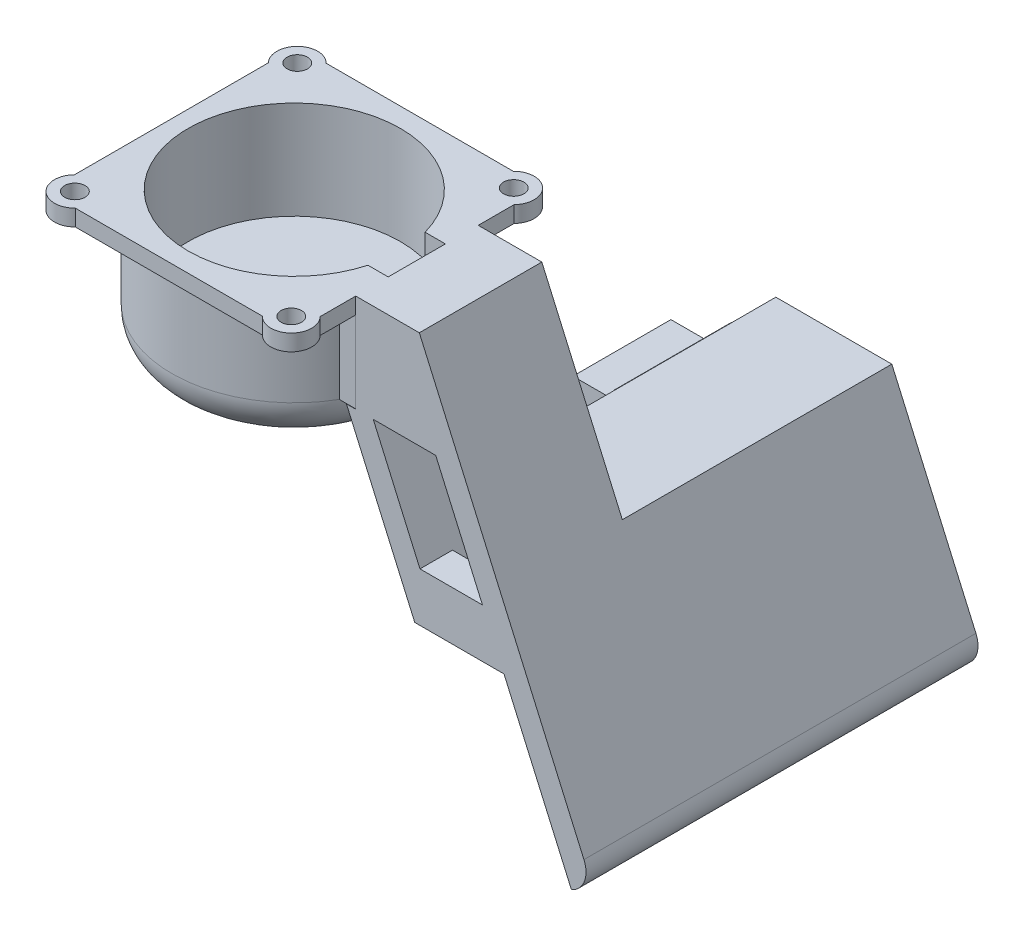
SolidWorks part; units mm, degrees
ref_plane "Front Plane" through (0, 0, 0) normal (0, 0, 1) x (1, 0, 0)
ref_plane "Top Plane" through (0, 0, 0) normal (0, 1, 0) x (1, 0, 0)
ref_plane "Right Plane" through (0, 0, 0) normal (1, 0, 0) x (0, 0, -1)
sketch "Sketch1" plane through (0, 0, 0) normal (0, 1, 0) x (1, 0, 0)
  line L0 (0, 15) -> (13, 15)
  line L1 (13, 15) -> (13, -15)
  line L2 (13, -15) -> (15, -15)
  line L3 (15, -15) -> (15, 15)
  line L4 (15, 15) -> (13, 15)
  circle A0 centre (0, 0) radius 13
  circle A1 centre (0, 0) radius 15
  dimension "D1" = 26
  dimension "D2" = 2
extrude "Boss-Extrude3" add sketch "Sketch1" along normal blind 12 contours L1 A1 A0 | L1 A1 | A1 L1 L2 L3 | A1 L3 L4 L1
sketch "Sketch4" plane through (0, 0, 0) normal (0, -1, 0) x (1, 0, 0)
  circle A0 centre (0, 0) radius 15
extrude "Boss-Extrude4" add sketch "Sketch4" along normal blind 5
fillet "Fillet4" radius 5 1 edges at (0, -5, -15)
sketch "Sketch7" plane through (15, 0, 0) normal (1, 0, 0) x (0, 0, -1)
  line L0 (-15, 0) -> (0, 0) construction
  line L1 (-3.5, 12) -> (3.5, 12)
  line L2 (-3.5, 12) -> (-3.5, 2)
  line L3 (-3.5, 2) -> (3.5, 2)
  line L4 (3.5, 12) -> (3.5, 2)
  line L6 (-15, 12) -> (-15, 0) construction
  dimension "D1" = 10
  dimension "D2" = 2
  dimension "D3" = 7
  dimension "D4" = 11.5
extrude "Cut-Extrude3" cut sketch "Sketch7" against normal blind 18
sketch "Sketch10" plane through (13, 0, 0) normal (-1, 0, 0) x (0, 0, 1)
  line L1 (-15, 12) -> (-7.4833, 12)
  line L2 (-15, 12) -> (-15, 0)
  line L3 (-15, 0) -> (-7.4833, 0)
  line L4 (-7.4833, 12) -> (-7.4833, 0)
  line L5 (7.4833, 12) -> (15, 12)
  line L6 (7.4833, 12) -> (7.4833, 0)
  line L7 (7.4833, 0) -> (15, 0)
  line L8 (15, 12) -> (15, 0)
extrude "Cut-Extrude4" cut sketch "Sketch10" against normal blind 18
sketch "Sketch11" plane through (0, 0, -7.4833) normal (0, 0, -1) x (-1, 0, 0)
  line L0 (-15, 0) -> (-26.4461, -25.9994)
  line L1 (-15, 12) -> (-22.8285, 12)
  line L2 (-22.8285, 12) -> (-40.97, -29.2075)
  line L3 (-26.4461, -25.9994) -> (-7.8394, -25.9994)
  line L4 (-40.97, -29.2075) -> (-44.8405, -37.9994)
  line L5 (-44.8405, -37.9994) -> (-8.2889, -37.9994)
  line L6 (-15, 2) -> (-16.3047, 2)
  line L7 (-15, 0) -> (-15, 12) construction
  line L8 (-16.3047, 2) -> (-29.5119, -27.9994)
  line L9 (-29.5119, -27.9994) -> (-4.9904, -27.9994)
  line L10 (-15, 9) -> (-20.8714, 9)
  line L11 (-20.8714, 9) -> (-40.2419, -34.9994)
  line L12 (-40.2419, -34.9994) -> (-10.0643, -34.9994)
  line L13 (-10.0643, -27.9994) -> (-10.0643, -25.9994)
  line L14 (-10.0643, -25.9994) -> (-10.0643, -27.9994)
  line L15 (-26.4461, -25.9994) -> (-15, 0)
  line L16 (-15, 2) -> (-16.3047, 2)
  line L17 (-15, 0) -> (-15, 2)
  line L18 (-15, 9) -> (-15, 12)
  line L19 (-15, 9) -> (-20.8714, 9)
  line L20 (-15, 12) -> (-22.8285, 12)
  line L21 (-10.0643, -34.9994) -> (-10.0643, -37.9994)
  line L22 (15, 0) -> (-13, 0) construction
  line M15 (-15, 12) -> (-15, 0)
  dimension "D1" = 12
  dimension "D2" = 12
  dimension "D3" = 2
  dimension "D4" = 2
  dimension "D5" = 3
  dimension "2" = 2
  dimension "D6" = 3
  dimension "D7" = 3
  dimension "D8" = 0
extrude "Boss-Extrude7" add sketch "Sketch11" against normal blind 15 contours L21 L12 L11 L10 L1 L2 L4 L5 M15 | L9 L13 L3 L0 L6 L8 M15
fillet "Fillet5" radius 2 2 edges at (26.4461, -25.9994, 0.0167) (29.5119, -27.9994, 0.0167)
fillet "Fillet6" radius 3 2 edges at (40.2419, -34.9994, 0.0167) (44.8405, -37.9994, 0.0167)
sketch "Sketch14" plane through (0, 0, -7.4833) normal (0, 0, -1) x (-1, 0, 0)
  line L0 (-10.0643, -27.9994) -> (-29.5119, -27.9994)
  line L1 (-29.5119, -27.9994) -> (-16.3047, 2)
  line L2 (-16.3047, 2) -> (-15, 2)
  line L3 (-15, 2) -> (-15, 9)
  line L4 (-15, 9) -> (-20.8714, 9)
  line L5 (-20.8714, 9) -> (-40.2419, -34.9994)
  line L6 (-40.2419, -34.9994) -> (-10.0643, -34.9994)
  line L7 (-10.0643, -34.9994) -> (-10.0643, -37.9994)
  line L8 (-10.0643, -37.9994) -> (-44.8405, -37.9994)
  line L9 (-44.8405, -37.9994) -> (-22.8285, 12)
  line L10 (-22.8285, 12) -> (-13, 12)
  line L11 (-13, 12) -> (-13, 0)
  line L12 (-13, 0) -> (-15, 0)
  line L15 (-10.0643, -26.3218) -> (-10.0643, -27.9994)
  line L16 (-22.8285, 12) -> (-42.9876, -33.7906) construction
  line L17 (-16.3047, 2) -> (-28.2766, -25.1935) construction
  line L18 (-15, 9) -> (-20.8714, 9) construction
  line L19 (-40.2419, -37.9994) -> (-10.0643, -37.9994) construction
  line L20 (-15, 2) -> (-15, 9) construction
  line L22 (-20.8714, 9) -> (-38.389, -30.7906) construction
  line L24 (-15, 2) -> (-16.3047, 2) construction
  line L25 (-15, 0) -> (-26.4461, -25.9994)
  line L26 (-26.4461, -25.9994) -> (-10.0643, -25.9994)
  line L27 (-23.3804, -25.9994) -> (-10.0643, -25.9994) construction
  line L28 (-35.6433, -34.9994) -> (-10.0643, -34.9994) construction
  line L29 (-10.0643, -27.9994) -> (-10.0643, -34.9994)
  line M16 (-10.0643, -34.9994) -> (-35.6433, -34.9994)
  arc M17 (-35.6433, -34.9994) -> (-38.389, -30.7906) centre (-35.6433, -31.9994) cw
  line M18 (-38.389, -30.7906) -> (-20.8714, 9)
  line M19 (-20.8714, 9) -> (-15, 9)
  line M20 (-15, 9) -> (-15, 2)
  line M21 (-15, 2) -> (-16.3047, 2)
  line M22 (-16.3047, 2) -> (-28.2766, -25.1935)
  arc M23 (-28.2766, -25.1935) -> (-26.4461, -27.9994) centre (-26.4461, -25.9994) ccw
  line M24 (-26.4461, -27.9994) -> (-10.0643, -27.9994)
  dimension "D1" = 0
  dimension "D2" = 0
  dimension "D3" = 0
  dimension "D4" = 0
  dimension "D5" = 0
  dimension "D6" = 0
  dimension "D7" = 0
extrude "Boss-Extrude10" add sketch "Sketch14" against normal blind 3.98 contours L29 L0 L1 M24 M22 M21 M20 M19 M18 M17 M16 | L1 L0 M23
sketch "Sketch16" plane through (0, 0, 7.5167) normal (0, 0, 1) x (1, 0, 0)
  line L0 (15, 0) -> (26.7788, -25.9994)
  line L1 (26.7788, -25.9994) -> (10.0643, -25.9994)
  line L2 (10.0643, -25.9994) -> (10.0643, -37.9994)
  line L3 (10.0643, -37.9994) -> (44.8405, -37.9994)
  line L4 (44.8405, -37.9994) -> (22.423, 12.921)
  line L6 (15, 12) -> (15, 0)
  line L7 (10.0643, -27.9994) -> (10.0643, -34.9994) construction
  line L8 (23.3804, -25.9994) -> (10.0643, -25.9994) construction
  line L9 (40.2419, -37.9994) -> (10.0643, -37.9994) construction
  line L10 (22.8285, 12) -> (42.9876, -33.7906) construction
  line L12 (15, 12) -> (22.8285, 12)
  line M5 (10.0643, -27.9994) -> (26.4461, -27.9994)
  arc M6 (26.4461, -27.9994) -> (28.2766, -25.1935) centre (26.4461, -25.9994) ccw
  line M7 (28.2766, -25.1935) -> (16.3047, 2)
  line M8 (16.3047, 2) -> (15, 2)
  dimension "D1" = 0
  dimension "D2" = 0
  dimension "D3" = 0
  dimension "D4" = 0
extrude "Boss-Extrude11" add sketch "Sketch16" against normal blind 3.98 contours L12 L6 L2 L3 L4 M8 M7 M6 M5
fillet "Fillet7" radius 3 1 edges at (44.8405, -37.9994, 5.5267)
sketch "Sketch17" plane through (0, 0, -7.4833) normal (0, 0, -1) x (-1, 0, 0)
  line L0 (-24.9133, -24.9994) -> (-13.9074, 0)
  line L1 (-24.9133, -24.9994) -> (-10.0643, -24.9994)
  line L2 (-10.0643, -24.9994) -> (-10.0643, -25.9994)
  line L3 (-10.0643, -25.9994) -> (-26.4461, -25.9994)
  line L4 (-26.4461, -25.9994) -> (-15, 0)
  line L5 (-15, 0) -> (-25.2109, -23.1935) construction
  line L6 (-23.3804, -25.9994) -> (-10.0643, -25.9994) construction
  line L7 (-10.0643, -25.9994) -> (-10.0643, -37.9994) construction
  line L8 (-15, 0) -> (-13, 0) construction
  line L9 (-15, 0) -> (-13.9074, 0)
  dimension "D1" = 1
  dimension "D2" = 1
extrude "Boss-Extrude12" add sketch "Sketch17" against normal up to surface (15 mm away)
fillet "Fillet8" radius 3 1 edges at (24.9133, -24.9994, 0.0167)
sketch "Sketch19" plane through (0, 12, 0) normal (0, 1, 0) x (1, 0, 0)
  line L0 (0, 0) -> (-18, 0)
  line L1 (-18, 0) -> (18, 0)
  line L2 (-18, 0) -> (-18, 18.5)
  line L3 (18, 0) -> (18, -18.5)
  line L4 (-18, 18.5) -> (18, -18.5)
  line L5 (-18, 18.5) -> (18, 18.5)
  line L6 (-18, 18.5) -> (-18, -18.5)
  line L7 (-18, -18.5) -> (18, -18.5)
  line L8 (18, 18.5) -> (18, -18.5)
  line L9 (18, 18.5) -> (-18, -18.5)
  line L10 (-15.4863, -12.3315) -> (-11.589, -8.326)
  line L11 (-11.589, -8.326) -> (-8.0054, -11.8127)
  line L12 (-8.0054, -11.8127) -> (-12.043, -15.9625)
  line L13 (-12.3179, 16.245) -> (-8.0328, 11.8409)
  line L14 (-8.0328, 11.8409) -> (-11.6164, 8.3541)
  line L15 (-11.6164, 8.3541) -> (-15.4967, 12.3422)
  line L16 (12.3268, 16.2541) -> (8.1521, 11.9635)
  line L17 (8.1521, 11.9635) -> (11.7358, 8.4768)
  line L18 (11.7358, 8.4768) -> (15.2536, 12.0924)
  line L19 (15.8076, -12.6618) -> (11.6323, -8.3704)
  line L20 (11.6323, -8.3704) -> (8.0486, -11.8572)
  line L21 (8.0486, -11.8572) -> (12.184, -16.1074)
  circle A0 centre (0, 0) radius 15
  circle A1 centre (-13.2497, -13.6178) radius 1.25
  circle A2 centre (-13.2497, 13.6178) radius 1.25
  circle A3 centre (13.2497, 13.6178) radius 1.25
  circle A4 centre (13.2497, -13.6178) radius 1.25
  circle A5 centre (-13.2497, 13.6178) radius 2.5
  circle A6 centre (-13.2497, -13.6178) radius 2.5
  circle A7 centre (13.2497, -13.6178) radius 2.5
  circle A8 centre (13.2497, 13.6178) radius 2.5
  arc M8 (13, 7.4833) -> (13, -7.4833) centre (0, 0) ccw
  dimension "D5" = 2.5
  dimension "D6" = 2.5
  dimension "D7" = 2.5
  dimension "D8" = 2.5
  dimension "D13" = 5
  dimension "D14" = 5
  dimension "D15" = 5
  dimension "D16" = 5
  dimension "D1" = 18
  dimension "D2" = 18
  dimension "D3" = 18.5
  dimension "D4" = 18.5
  dimension "D9" = 19
  dimension "D10" = 19
  dimension "D11" = 19
  dimension "D12" = 19
extrude "Boss-Extrude13" add sketch "Sketch19" against normal blind 2 contours L4 A7 A4 | L4 A7 A4 | A7 L19 L4 M8 | A7 L4 L21 M8 | L20 L21 L4 M8 | L19 L20 L4 M8 | L9 A8 A3 | A8 L9 A3 | A8 L16 L9 M8 | A8 L9 L18 M8 | L17 L18 L9 M8 | L16 L17 L9 M8 | L4 A5 A2 | A5 L15 L4 M8 | A5 L4 L13 M8 | L14 L13 L4 M8 | L15 L14 L4 M8 | L4 A5 A2 | A6 L9 L10 M8 | A6 L12 L9 M8 | L12 L11 L9 M8 | L11 L10 L9 M8 | L9 A6 A1 | A6 L9 A1
sketch "Sketch22" plane through (0, 0, -7.4833) normal (0, 0, -1) x (-1, 0, 0)
  line L0 (-10.0643, -24.9994) -> (-20.3147, -24.9994) construction
  line L1 (-10.0643, -37.9994) -> (-16.0643, -37.9994)
  line L2 (-10.0643, -37.9994) -> (-10.0643, -24.9994)
  line L3 (-10.0643, -24.9994) -> (-16.0643, -24.9994)
  line L4 (-16.0643, -37.9994) -> (-16.0643, -24.9994)
  dimension "D1" = 6
extrude "Cut-Extrude6" cut sketch "Sketch22" against normal blind 33
sketch "Sketch27" plane through (0, 0, -7.4833) normal (0, 0, -1) x (-1, 0, 0)
  line L0 (-16.0643, -24.9994) -> (-20.3147, -24.9994)
  line L1 (-20.3147, -24.9994) -> (-23.0604, -20.7906)
  line L2 (-23.0604, -20.7906) -> (-37.2644, -20.7906)
  line L3 (-22.8285, 12) -> (-42.9876, -33.7906) construction
  line L4 (-37.2644, -20.7906) -> (-42.9876, -33.7906)
  line L5 (-42.9876, -33.7906) -> (-40.2419, -37.9994)
  line L6 (-40.2419, -37.9994) -> (-16.0643, -37.9994)
  line L7 (-16.0643, -37.9994) -> (-16.0643, -24.9994)
  line L8 (-24.6852, -23.7906) -> (-35.3073, -23.7906)
  line L9 (-35.3073, -23.7906) -> (-39.5873, -33.5123)
  line L10 (-39.5873, -33.5123) -> (-38.6171, -34.9994)
  line L11 (-38.6171, -34.9994) -> (-19.0643, -34.9994)
  line L12 (-19.0643, -34.9994) -> (-19.0643, -27.9994)
  line L13 (-19.0643, -27.9994) -> (-21.9395, -27.9994)
  line L14 (-21.9395, -27.9994) -> (-24.6852, -23.7906)
  circle A0 centre (-40.2419, -34.9994) radius 3
  circle A1 centre (-20.3147, -21.9994) radius 3
  line M2 (-40.2419, -37.9994) -> (-16.0643, -37.9994)
  line M3 (-16.0643, -37.9994) -> (-16.0643, -24.9994)
  line M4 (-16.0643, -24.9994) -> (-20.3147, -24.9994)
  arc M5 (-20.3147, -24.9994) -> (-23.0604, -20.7906) centre (-20.3147, -21.9994) cw
  line M10 (-22.8285, 12) -> (-42.9876, -33.7906)
  arc M11 (-42.9876, -33.7906) -> (-40.2419, -37.9994) centre (-40.2419, -34.9994) ccw
  dimension "D1" = 3
extrude "Boss-Extrude20" add sketch "Sketch27" along normal blind 30 contours A0 L9 L8 L14 L13 L12 L11 L2 M2 M3 M4 M5 M10 | L9 A0 L5 L11 L10 | L5 M11
sketch "Sketch28" plane through (0, 0, -37.4833) normal (0, 0, -1) x (-1, 0, 0)
  line L0 (-23.0604, -20.7906) -> (-20.3147, -24.9994)
  line L1 (-20.3147, -24.9994) -> (-16.0643, -24.9994)
  line L2 (-16.0643, -24.9994) -> (-16.0643, -37.9994)
  line L3 (-16.0643, -37.9994) -> (-40.2419, -37.9994)
  line L4 (-40.2419, -37.9994) -> (-42.9876, -33.7906)
  line L5 (-42.9876, -33.7906) -> (-37.2644, -20.7906)
  line L6 (-37.2644, -20.7906) -> (-23.0604, -20.7906)
  circle A0 centre (-40.2419, -34.9994) radius 3
  circle A1 centre (-20.3147, -21.9994) radius 3
  line M1 (-37.2644, -20.7906) -> (-42.9876, -33.7906)
  arc M2 (-42.9876, -33.7906) -> (-40.2419, -37.9994) centre (-40.2419, -34.9994) ccw
  line M3 (-40.2419, -37.9994) -> (-16.0643, -37.9994)
  line M4 (-16.0643, -37.9994) -> (-16.0643, -24.9994)
  line M5 (-16.0643, -24.9994) -> (-20.3147, -24.9994)
  arc M6 (-20.3147, -24.9994) -> (-23.0604, -20.7906) centre (-20.3147, -21.9994) cw
  line M7 (-23.0604, -20.7906) -> (-37.2644, -20.7906)
  line M8 (-38.6171, -34.9994) -> (-39.5873, -33.5123)
  line M9 (-39.5873, -33.5123) -> (-35.3073, -23.7906)
  line M10 (-35.3073, -23.7906) -> (-24.6852, -23.7906)
  line M11 (-24.6852, -23.7906) -> (-21.9395, -27.9994)
  line M12 (-21.9395, -27.9994) -> (-19.0643, -27.9994)
  line M13 (-19.0643, -27.9994) -> (-19.0643, -34.9994)
  line M14 (-19.0643, -34.9994) -> (-38.6171, -34.9994)
extrude "Boss-Extrude21" add sketch "Sketch28" along normal blind 3 contours L4 M2 | A0 L4 M9 M14 M8 | A0 M9 M10 M11 M12 M13 M14 M3 M4 M5 M6 M7 M1 | A0 M14 M13 M12 M11 M10 M9 | A0 M14 M9 M8
sketch "Sketch29" plane through (16.0643, 0, 0) normal (-1, 0, 0) x (0, 0, 1)
  line L0 (-40.4833, -37.9994) -> (-40.4833, -24.9994) construction
  line L1 (-40.4833, -15.77) -> (-26.0534, -15.77)
  line L2 (-40.4833, -15.77) -> (-40.4833, -43.02)
  line L3 (-40.4833, -43.02) -> (-26.0534, -43.02)
  line L4 (-26.0534, -15.77) -> (-26.0534, -43.02)
  line L5 (-40.4833, -20.7906) -> (-7.4833, -20.7906) construction
  line L6 (-37.267, -20.7906) -> (-33.966, -20.7906)
  line L7 (-37.267, -20.7906) -> (-37.267, -37.9994)
  line L8 (-37.267, -37.9994) -> (-33.966, -37.9994)
  line L9 (-33.966, -20.7906) -> (-33.966, -37.9994)
  line L10 (7.5167, -37.9994) -> (-40.4833, -37.9994) construction
  line L11 (-37.267, -29.395) -> (-30.6651, -29.395)
  dimension "D1" = 0
  dimension "D2" = 0
  dimension "D3" = 0
  dimension "D4" = 13.625
  dimension "D5" = 13.625
extrude "Boss-Extrude22" add sketch "Sketch29" along normal blind 3
sketch "Sketch30" plane through (13.0643, 0, 0) normal (-1, 0, 0) x (0, 0, 1)
  line L0 (-26.0534, -15.77) -> (-26.0534, -43.02) construction
  line L1 (-40.4833, -15.77) -> (-26.0534, -15.77) construction
  line L2 (-40.4833, -43.02) -> (-26.0534, -43.02) construction
  circle A0 centre (-29.0534, -19.77) radius 1.25
  circle A1 centre (-35.0534, -19.77) radius 1.25
  circle A2 centre (-35.0534, -39.02) radius 1.25
  circle A3 centre (-29.0534, -39.02) radius 1.25
  dimension "D1" = 2.5
  dimension "D2" = 2.5
  dimension "D3" = 2.5
  dimension "D4" = 2.5
  dimension "D5" = 3
  dimension "D6" = 3
  dimension "D7" = 6
  dimension "D8" = 6
  dimension "D9" = 4
  dimension "D10" = 4
  dimension "D11" = 4
extrude "Cut-Extrude7" cut sketch "Sketch30" against normal blind 8
sketch "Sketch31" plane through (0, -37.9994, 0) normal (0, -1, 0) x (1, 0, 0)
  line L0 (16.0643, -26.0534) -> (16.0643, -28.3317) construction
  line L1 (16.0643, -28.3317) -> (21.0643, -28.3317)
  line L2 (16.0643, -28.3317) -> (16.0643, -35.7751)
  line L3 (16.0643, -35.7751) -> (21.0643, -35.7751)
  line L4 (21.0643, -28.3317) -> (21.0643, -35.7751)
  line L5 (21.4231, -30.2751) -> (16.0643, -30.2751)
  line L6 (21.4231, -30.2751) -> (21.4231, -27.8317)
  line L7 (21.4231, -27.8317) -> (16.0643, -27.8317)
  line L8 (16.0643, -30.2751) -> (16.0643, -27.8317)
  line L9 (16.0643, -29.7751) -> (21.0643, -29.7751) construction
  line L10 (21.6057, -36.2751) -> (16.0643, -36.2751)
  line L11 (21.6057, -36.2751) -> (21.6057, -33.8317)
  line L12 (21.6057, -33.8317) -> (16.0643, -33.8317)
  line L13 (16.0643, -36.2751) -> (16.0643, -33.8317)
  line L14 (21.0643, -34.3317) -> (16.0643, -34.3317) construction
  line M5 (16.0643, -28.3317) -> (21.0643, -28.3317)
  line M6 (21.0643, -28.3317) -> (21.0643, -29.7751)
  line M7 (21.0643, -29.7751) -> (16.0643, -29.7751)
  line M8 (16.0643, -29.7751) -> (16.0643, -34.3317)
  line M9 (16.0643, -34.3317) -> (21.0643, -34.3317)
  line M10 (21.0643, -34.3317) -> (21.0643, -35.7751)
  line M11 (21.0643, -35.7751) -> (16.0643, -35.7751)
  line M12 (16.0643, -35.7751) -> (16.0643, -40.4833)
  line M18 (16.0643, -26.0534) -> (16.0643, -28.3317)
  dimension "D1" = 0.5
  dimension "D2" = 0.5
  dimension "D3" = 0.5
  dimension "D4" = 0.5
extrude "Cut-Extrude9" cut sketch "Sketch31" against normal blind 0.6 contours L6 L7 L4 L5 M18 M5 M6 | L2 M5 M7 M6 | L5 L4 M7 M8 | L4 L12 M8 M9 | L2 M9 M11 M10 | L11 L12 L4 L10 M10 M11 M12
sketch "Sketch32" plane through (13.0643, 0, 0) normal (-1, 0, 0) x (0, 0, 1)
  line L0 (-40.4833, -20.7906) -> (-7.4833, -20.7906) construction
  line L1 (-38.0534, -16.77) -> (-26.0534, -16.77)
  line L2 (-38.0534, -16.77) -> (-38.0534, -23.7906)
  line L3 (-38.0534, -23.7906) -> (-26.0534, -23.7906)
  line L4 (-26.0534, -16.77) -> (-26.0534, -23.7906)
  line L5 (-38.0534, -34.9994) -> (-26.0534, -34.9994)
  line L6 (-38.0534, -34.9994) -> (-38.0534, -42.02)
  line L7 (-38.0534, -42.02) -> (-26.0534, -42.02)
  line L8 (-26.0534, -34.9994) -> (-26.0534, -42.02)
  line L9 (-36.2751, -37.9994) -> (-33.8317, -37.9994) construction
  circle A0 centre (-29.0534, -19.77) radius 1.25 construction
  circle A1 centre (-35.0534, -19.77) radius 1.25 construction
  circle A2 centre (-35.0534, -39.02) radius 1.25 construction
  circle A3 centre (-29.0534, -39.02) radius 1.25 construction
  circle A4 centre (-35.0534, -19.77) radius 1.25
  circle A5 centre (-29.0534, -19.77) radius 1.25
  circle A6 centre (-29.0534, -39.02) radius 1.25
  circle A7 centre (-35.0534, -39.02) radius 1.25
  point P10 (-32.0534, -23.7906)
  dimension "D3" = 3
  dimension "D4" = 3
  dimension "D7" = 3
  dimension "D8" = 3
  dimension "D1" = 3
  dimension "D2" = 3
  dimension "D5" = 3
  dimension "D6" = 3
extrude "Boss-Extrude23" add sketch "Sketch32" along normal blind 12
sketch "Sketch33" plane through (0, 0, 7.5167) normal (0, 0, 1) x (1, 0, 0)
  line L0 (16.0643, -24.9994) -> (20.3147, -24.9994)
  line L1 (20.3147, -24.9994) -> (20.3147, -37.9994)
  line L2 (40.2419, -37.9994) -> (16.0643, -37.9994) construction
  line L3 (20.3147, -37.9994) -> (16.0643, -37.9994)
  line L4 (16.0643, -37.9994) -> (16.0643, -24.9994)
extrude "Cut-Extrude10" cut sketch "Sketch33" against normal blind 15
sketch "Sketch35" plane through (0, 0, -7.4833) normal (0, 0, 1) x (1, 0, 0)
  line L1 (19.0643, -27.9994) -> (20.3147, -27.9994)
  line L2 (19.0643, -27.9994) -> (19.0643, -34.9994)
  line L3 (19.0643, -34.9994) -> (20.3147, -34.9994)
  line L4 (20.3147, -27.9994) -> (20.3147, -34.9994)
  line L5 (16.0643, -24.9994) -> (20.3147, -24.9994)
  line L6 (16.0643, -24.9994) -> (16.0643, -37.9994)
  line L7 (16.0643, -37.9994) -> (20.3147, -37.9994)
  line L8 (20.3147, -24.9994) -> (20.3147, -37.9994)
  line M1 (20.3147, -34.9994) -> (19.0643, -34.9994)
  line M2 (19.0643, -34.9994) -> (19.0643, -27.9994)
  line M3 (19.0643, -27.9994) -> (20.3147, -27.9994)
  line M4 (20.3147, -27.9994) -> (20.3147, -24.9994)
  line M5 (20.3147, -24.9994) -> (16.0643, -24.9994)
  line M6 (16.0643, -24.9994) -> (16.0643, -37.9994)
  line M7 (16.0643, -37.9994) -> (20.3147, -37.9994)
  line M8 (20.3147, -37.9994) -> (20.3147, -34.9994)
extrude "Boss-Extrude31" add sketch "Sketch35" along normal blind 1 contours M8 M1 M2 M3 M4 M5 M6 M7 | L4 M3 M2 M1
sketch "Sketch38" plane through (0, 0, 7.5167) normal (0, 0, 1) x (1, 0, 0)
  line L0 (20.3147, -24.9994) -> (20.3147, -37.9994)
  line L1 (20.3147, -37.9994) -> (40.2419, -37.9994)
  line L2 (40.2419, -37.9994) -> (42.9876, -33.7906)
  line L3 (42.9876, -33.7906) -> (39.1173, -24.9994)
  line L4 (22.8285, 12) -> (42.9876, -33.7906) construction
  line L5 (39.1173, -24.9994) -> (20.3147, -24.9994)
  line L6 (39.1173, -24.9994) -> (36.4759, -18.9994)
  line L7 (36.4759, -18.9994) -> (20.3147, -18.9994)
  circle A0 centre (20.3147, -21.9994) radius 3
  circle A1 centre (40.2419, -34.9994) radius 3
  arc M1 (23.0604, -20.7906) -> (20.3147, -24.9994) centre (20.3147, -21.9994) cw
  line M2 (20.3147, -24.9994) -> (20.3147, -37.9994)
  line M3 (20.3147, -37.9994) -> (40.2419, -37.9994)
  arc M4 (40.2419, -37.9994) -> (42.9876, -33.7906) centre (40.2419, -34.9994) ccw
  line M5 (42.9876, -33.7906) -> (22.8285, 12)
  line M9 (13.9074, 0) -> (23.0604, -20.7906)
extrude "Cut-Extrude16" cut sketch "Sketch38" against normal blind 11 contours L7 L5 M5 M9 M1 | A1 L5 M5 M2 M3 | L2 A1 | L2 M4
sketch "Sketch40" plane through (0, 0, -6.4833) normal (0, 0, 1) x (1, 0, 0)
  line L1 (16.0643, -24.9994) -> (20.3147, -24.9994)
  line L2 (16.0643, -24.9994) -> (16.0643, -37.9994)
  line L3 (16.0643, -37.9994) -> (20.3147, -37.9994)
  line L4 (20.3147, -24.9994) -> (20.3147, -37.9994)
extrude "Boss-Extrude32" add sketch "Sketch40" along normal blind 3
sketch "Sketch41" plane through (0, 0, -7.4833) normal (0, 0, -1) x (-1, 0, 0)
  line L0 (-23.0604, -20.7906) -> (-19.5384, -12.7906)
  line L1 (-23.0604, -20.7906) -> (-13.9074, 0) construction
  line L2 (-19.5384, -12.7906) -> (-33.7425, -12.7906)
  line L3 (-22.8285, 12) -> (-37.2644, -20.7906) construction
  line L4 (-33.7425, -12.7906) -> (-37.2644, -20.7906)
  line L5 (-23.0604, -20.7906) -> (-37.2644, -20.7906) construction
  line L6 (-19.5384, -15.7906) -> (-31.7853, -15.7906)
  line L7 (-31.7853, -15.7906) -> (-34.5187, -21.9994)
  line L8 (-25.8061, -19.5818) -> (-22.2841, -11.5818)
  line L10 (-37.2644, -20.7906) -> (-23.0604, -20.7906)
  line L11 (-37.2644, -17.7906) -> (-23.0604, -17.7906)
  dimension "D1" = 8
  dimension "D2" = 3
  dimension "D3" = 3
  dimension "D4" = 3
extrude "Boss-Extrude33" add sketch "Sketch41" along normal up to surface (33 mm away) up to face at (23.3213, -29.1306, -40.4833)
sketch "Sketch42" plane through (0, 0, -40.4833) normal (0, 0, -1) x (-1, 0, 0)
  line L0 (-33.7425, -12.7906) -> (-42.9876, -33.7906)
  line L1 (-42.9876, -33.7906) -> (-40.2419, -37.9994)
  line L2 (-40.2419, -37.9994) -> (-16.0643, -37.9994)
  line L3 (-16.0643, -37.9994) -> (-16.0643, -24.9994)
  line L4 (-16.0643, -24.9994) -> (-20.3147, -24.9994)
  line L5 (-20.3147, -24.9994) -> (-23.0604, -20.7906)
  line L6 (-23.0604, -20.7906) -> (-19.5384, -12.7906)
  line L7 (-19.5384, -12.7906) -> (-33.7425, -12.7906)
  circle A0 centre (-40.2419, -34.9994) radius 3
  circle A1 centre (-20.3147, -21.9994) radius 3
  line M1 (-33.7425, -12.7906) -> (-42.9876, -33.7906)
  line M3 (-40.2419, -37.9994) -> (-16.0643, -37.9994)
  line M9 (-16.0643, -24.9994) -> (-20.3147, -24.9994)
  arc M10 (-20.3147, -24.9994) -> (-23.0604, -20.7906) centre (-20.3147, -21.9994) cw
  line M11 (-23.0604, -20.7906) -> (-19.5384, -12.7906)
  line M12 (-19.5384, -12.7906) -> (-33.7425, -12.7906)
  line M13 (-25.0175, -17.7906) -> (-32.6658, -17.7906)
  line M14 (-32.6658, -17.7906) -> (-31.7853, -15.7906)
  line M15 (-31.7853, -15.7906) -> (-24.137, -15.7906)
  line M16 (-24.137, -15.7906) -> (-25.0175, -17.7906)
extrude "Cut-Extrude18" cut sketch "Sketch42" against normal blind 33 contours A0 L3 M3 M9 M10 M11 M12 M1 M16 M13 M14 M15 | L5 M10 | M13 M16 M15 M14
sketch "Sketch43" plane through (0, 0, -7.4833) normal (0, 0, -1) x (-1, 0, 0)
  line L0 (-18.4839, -10.3953) -> (-32.6879, -10.3953)
  line L1 (-23.0604, -20.7906) -> (-13.9074, 0) construction
  line L2 (-22.8285, 12) -> (-42.9876, -33.7906) construction
  line L3 (-32.6879, -10.3953) -> (-42.9876, -33.7906)
  line L4 (-42.9876, -33.7906) -> (-40.2419, -37.9994)
  line L5 (-40.2419, -37.9994) -> (-16.0643, -37.9994)
  line L6 (-16.0643, -37.9994) -> (-16.0643, -24.9994)
  line L7 (-16.0643, -24.9994) -> (-20.3147, -24.9994)
  line L8 (-20.3147, -24.9994) -> (-23.0604, -20.7906)
  line L9 (-23.0604, -20.7906) -> (-18.4839, -10.3953)
  line L10 (-30.7308, -13.3953) -> (-39.5873, -33.5123)
  line L11 (-39.5873, -33.5123) -> (-38.6171, -34.9994)
  line L12 (-38.6171, -34.9994) -> (-19.0643, -34.9994)
  line L13 (-19.0643, -34.9994) -> (-19.0643, -27.9994)
  line L14 (-19.0643, -27.9994) -> (-21.9395, -27.9994)
  line L15 (-21.9395, -27.9994) -> (-26.4608, -21.0689)
  line L16 (-26.4608, -21.0689) -> (-23.0825, -13.3953)
  line L17 (-23.0825, -13.3953) -> (-30.7308, -13.3953)
  circle A0 centre (-40.2419, -34.9994) radius 3
  circle A1 centre (-20.3147, -21.9994) radius 3
  line M9 (-22.8285, 12) -> (-42.9876, -33.7906)
  arc M10 (-42.9876, -33.7906) -> (-40.2419, -37.9994) centre (-40.2419, -34.9994) ccw
  line M11 (-40.2419, -37.9994) -> (-16.0643, -37.9994)
  line M12 (-16.0643, -37.9994) -> (-16.0643, -24.9994)
  line M13 (-16.0643, -24.9994) -> (-20.3147, -24.9994)
  arc M14 (-20.3147, -24.9994) -> (-23.0604, -20.7906) centre (-20.3147, -21.9994) cw
  line M15 (-23.0604, -20.7906) -> (-13.9074, 0)
  dimension "D1" = 3
extrude "Boss-Extrude34" add sketch "Sketch43" along normal up to surface (33 mm away) contours A0 L10 L17 L16 L15 L14 L13 L12 L0 M11 M12 M13 M14 M15 M9 | L10 A0 L4 L12 L11 | L4 M10
sketch "Sketch44" plane through (0, 0, -40.4833) normal (0, 0, -1) x (-1, 0, 0)
  line L0 (-18.4839, -10.3953) -> (-23.0604, -20.7906)
  line L1 (-23.0604, -20.7906) -> (-20.3147, -24.9994)
  line L2 (-20.3147, -24.9994) -> (-16.0643, -24.9994)
  line L3 (-16.0643, -24.9994) -> (-16.0643, -37.9994)
  line L4 (-16.0643, -37.9994) -> (-40.2419, -37.9994)
  line L5 (-40.2419, -37.9994) -> (-42.9876, -33.7906)
  line L6 (-42.9876, -33.7906) -> (-32.6879, -10.3953)
  line L7 (-32.6879, -10.3953) -> (-18.4839, -10.3953)
  circle A0 centre (-20.3147, -21.9994) radius 3
  circle A1 centre (-40.2419, -34.9994) radius 3
  line M2 (-38.6171, -34.9994) -> (-39.5873, -33.5123)
  line M3 (-39.5873, -33.5123) -> (-30.7308, -13.3953)
  line M4 (-30.7308, -13.3953) -> (-23.0825, -13.3953)
  line M5 (-23.0825, -13.3953) -> (-26.4608, -21.0689)
  line M6 (-26.4608, -21.0689) -> (-21.9395, -27.9994)
  line M7 (-21.9395, -27.9994) -> (-19.0643, -27.9994)
  line M8 (-19.0643, -27.9994) -> (-19.0643, -34.9994)
  line M9 (-19.0643, -34.9994) -> (-38.6171, -34.9994)
  line M10 (-18.4839, -10.3953) -> (-32.6879, -10.3953)
  line M11 (-32.6879, -10.3953) -> (-42.9876, -33.7906)
  arc M12 (-42.9876, -33.7906) -> (-40.2419, -37.9994) centre (-40.2419, -34.9994) ccw
  line M13 (-40.2419, -37.9994) -> (-16.0643, -37.9994)
  line M19 (-16.0643, -24.9994) -> (-20.3147, -24.9994)
  arc M20 (-20.3147, -24.9994) -> (-23.0604, -20.7906) centre (-20.3147, -21.9994) cw
  line M21 (-23.0604, -20.7906) -> (-18.4839, -10.3953)
extrude "Boss-Extrude36" add sketch "Sketch44" against normal blind 37 contours A1 M9 M8 M7 M6 M5 M4 M3 | A1 L3 M3 M4 M5 M6 M7 M8 M9 M13 M19 M20 M21 M10 M11 | A1 L5 M3 M9 M2 | A1 M9 M3 M2 | L5 M12
sketch "Sketch45" plane through (16.0643, 0, 0) normal (-1, 0, 0) x (0, 0, 1)
  line L0 (-3.4833, -37.9994) -> (-26.0534, -37.9994) construction
  line L1 (-3.4833, -18.9994) -> (-7.4833, -18.9994)
  line L2 (-3.4833, -18.9994) -> (-3.4833, -37.9994)
  line L3 (-3.4833, -37.9994) -> (-7.4833, -37.9994)
  line L4 (-7.4833, -18.9994) -> (-7.4833, -37.9994)
extrude "Cut-Extrude21" cut sketch "Sketch45" against normal blind 29
sketch "Sketch47" plane through (0, 0, -40.4833) normal (0, 0, -1) x (-1, 0, 0)
  line L0 (-30.7308, -13.3953) -> (-40.2419, -34.9994)
  line L1 (-40.2419, -34.9994) -> (-16.0643, -34.9994)
  line L2 (-16.0643, -34.9994) -> (-16.0643, -27.9994)
  line L3 (-16.0643, -27.9994) -> (-29.5119, -27.9994)
  line L4 (-29.5119, -27.9994) -> (-23.0825, -13.3953)
  line L5 (-23.0825, -13.3953) -> (-30.7308, -13.3953)
  line L6 (-18.4839, -10.3953) -> (-32.6879, -10.3953) construction
  line L7 (-32.6879, -10.3953) -> (-42.9876, -33.7906) construction
  line L8 (-40.2419, -37.9994) -> (-16.0643, -37.9994) construction
  line L9 (-18.4839, -10.3953) -> (-32.6879, -10.3953) construction
  line L10 (-13.0643, -15.77) -> (-13.0643, -43.02) construction
  line L11 (-16.0643, -24.9994) -> (-20.3147, -24.9994) construction
  line L12 (-23.0604, -20.7906) -> (-18.4839, -10.3953) construction
  circle A0 centre (-40.2419, -34.9994) radius 3
  dimension "D1" = 3
  dimension "D2" = 3
  dimension "D3" = 3
  dimension "D4" = 3
  dimension "D5" = 3
  dimension "D6" = 3
extrude "Cut-Extrude22" cut sketch "Sketch47" against normal blind 26 contours A0 L1 L2 L3 L4 L5 L0
sketch "Sketch48" plane through (0, 0, -40.4833) normal (0, 0, -1) x (-1, 0, 0)
  line L0 (-32.6879, -10.3953) -> (-18.4839, -10.3953)
  line L1 (-18.4839, -10.3953) -> (-23.0604, -20.7906)
  line L2 (-23.0604, -20.7906) -> (-20.3147, -24.9994)
  line L3 (-20.3147, -24.9994) -> (-16.0643, -24.9994)
  line L4 (-16.0643, -24.9994) -> (-16.0643, -37.9994)
  line L5 (-16.0643, -37.9994) -> (-40.2419, -37.9994)
  line L6 (-40.2419, -37.9994) -> (-42.9876, -33.7906)
  line L7 (-42.9876, -33.7906) -> (-32.6879, -10.3953)
  circle A0 centre (-40.2419, -34.9994) radius 3
  circle A1 centre (-20.3147, -21.9994) radius 3
  line M9 (-40.2419, -37.9994) -> (-16.0643, -37.9994)
  line M15 (-16.0643, -24.9994) -> (-20.3147, -24.9994)
  arc M16 (-20.3147, -24.9994) -> (-23.0604, -20.7906) centre (-20.3147, -21.9994) cw
  line M17 (-23.0604, -20.7906) -> (-18.4839, -10.3953)
  line M18 (-18.4839, -10.3953) -> (-32.6879, -10.3953)
  line M19 (-32.6879, -10.3953) -> (-42.9876, -33.7906)
  arc M20 (-42.9876, -33.7906) -> (-40.2419, -37.9994) centre (-40.2419, -34.9994) ccw
  line M21 (-16.0643, -34.9994) -> (-37.2419, -34.9994)
  arc M22 (-37.2419, -34.9994) -> (-39.0332, -32.2537) centre (-40.2419, -34.9994) ccw
  line M23 (-39.0332, -32.2537) -> (-30.7308, -13.3953)
  line M24 (-30.7308, -13.3953) -> (-23.0825, -13.3953)
  line M25 (-23.0825, -13.3953) -> (-29.5119, -27.9994)
  line M26 (-29.5119, -27.9994) -> (-16.0643, -27.9994)
  line M27 (-16.0643, -27.9994) -> (-16.0643, -34.9994)
extrude "Boss-Extrude41" add sketch "Sketch48" against normal blind 5 contours L6 M20 | A0 L6 M22 | A0 L4 M23 M24 M25 M26 M15 M16 M17 M18 M19 | A0 L4 M9 M21 | M21 M27 M26 M25 M24 M23 M22
sketch "Sketch49" plane through (16.0643, 0, 0) normal (-1, 0, 0) x (0, 0, 1)
  line L1 (-7.4833, -37.9994) -> (-40.4833, -37.9994)
  line L2 (-7.4833, -37.9994) -> (-7.4833, -24.9994)
  line L3 (-7.4833, -24.9994) -> (-40.4833, -24.9994)
  line L4 (-40.4833, -37.9994) -> (-40.4833, -24.9994)
extrude "Boss-Extrude42" add sketch "Sketch49" against normal blind 3
sketch "Sketch50" plane through (0, 0, -7.4833) normal (0, 0, 1) x (1, 0, 0)
  line L0 (36.4759, -18.9994) -> (44.8405, -37.9994)
  line L1 (44.8405, -37.9994) -> (41.5627, -37.9994)
  line L2 (41.5627, -37.9994) -> (33.198, -18.9994)
  line L3 (36.4759, -18.9994) -> (22.2718, -18.9994) construction
  line L4 (40.2419, -37.9994) -> (16.0643, -37.9994) construction
  line L5 (42.9876, -33.7906) -> (36.4759, -18.9994) construction
  circle A0 centre (40.2419, -34.9994) radius 3
  dimension "D1" = 0
  dimension "D2" = 3
extrude "Boss-Extrude44" add sketch "Sketch50" along normal blind 15
sketch "Sketch51" plane through (1.0643, 0, 0) normal (-1, 0, 0) x (0, 0, 1)
  line L1 (-38.0534, -16.77) -> (-26.0534, -16.77)
  line L2 (-38.0534, -16.77) -> (-38.0534, -23.7906)
  line L3 (-38.0534, -23.7906) -> (-26.0534, -23.7906)
  line L4 (-26.0534, -16.77) -> (-26.0534, -23.7906)
  line L5 (-38.0534, -34.9994) -> (-26.0534, -34.9994)
  line L6 (-38.0534, -34.9994) -> (-38.0534, -42.02)
  line L7 (-38.0534, -42.02) -> (-26.0534, -42.02)
  line L8 (-26.0534, -34.9994) -> (-26.0534, -42.02)
extrude "Cut-Extrude23" cut sketch "Sketch51" against normal blind 7
sketch "Sketch53" plane through (0, 0, -7.4833) normal (0, 0, 1) x (1, 0, 0)
  line L0 (22.2718, -18.9994) -> (33.198, -18.9994)
  line L1 (33.198, -18.9994) -> (41.4507, -37.7451)
  line L3 (16.0643, -37.9994) -> (16.0643, -24.9994)
  line L4 (16.0643, -24.9994) -> (20.3147, -24.9994)
  line L5 (20.3147, -24.9994) -> (23.0604, -20.7906)
  line L6 (22.2718, -18.9994) -> (23.0604, -20.7906)
  line L7 (16.0643, -37.9994) -> (40.2419, -37.9994)
  circle A0 centre (20.3147, -21.9994) radius 3
  circle A1 centre (40.2419, -34.9994) radius 3
  arc M1 (40.2419, -37.9994) -> (41.4507, -37.7451) centre (40.2419, -34.9994) ccw
  line M2 (41.4507, -37.7451) -> (33.198, -18.9994)
  line M3 (33.198, -18.9994) -> (22.2718, -18.9994)
  line M4 (22.2718, -18.9994) -> (23.0604, -20.7906)
  arc M5 (23.0604, -20.7906) -> (20.3147, -24.9994) centre (20.3147, -21.9994) cw
  line M6 (20.3147, -24.9994) -> (16.0643, -24.9994)
  line M7 (16.0643, -24.9994) -> (16.0643, -37.9994)
  line M8 (16.0643, -37.9994) -> (40.2419, -37.9994)
extrude "Cut-Extrude24" cut sketch "Sketch53" against normal blind 2 contours A1 L1 M3 M4 M5 M6 M7 M8 | A1 M2 M1
fillet "Fillet10" radius 3 1 edges at (16.0643, -31.4994, -9.4833)
sketch "Sketch54" plane through (0, -37.9994, 0) normal (0, -1, 0) x (1, 0, 0)
  line L0 (16.0643, -29.0534) -> (19.867, -29.0534)
  line L1 (16.0643, -28.3317) -> (16.0643, -29.7751) construction
  line L2 (16.0643, -35.0534) -> (20.1904, -35.0534)
  line L3 (16.0643, -34.3317) -> (16.0643, -35.7751) construction
  line L4 (16.0643, -29.7751) -> (16.0643, -34.3317) construction
  line L5 (16.0643, -27.0534) -> (20.0643, -27.0534)
  line L6 (16.0643, -27.0534) -> (16.0643, -31.0534)
  line L7 (16.0643, -31.0534) -> (20.0643, -31.0534)
  line L8 (20.0643, -27.0534) -> (20.0643, -31.0534)
  line L9 (16.0643, -33.0534) -> (20.0643, -33.0534)
  line L10 (16.0643, -33.0534) -> (16.0643, -37.0534)
  line L11 (16.0643, -37.0534) -> (20.0643, -37.0534)
  line L12 (20.0643, -33.0534) -> (20.0643, -37.0534)
  dimension "D1" = 2
  dimension "D2" = 2
  dimension "D3" = 2
  dimension "D4" = 2
  dimension "D5" = 0
  dimension "D6" = 0
  dimension "D7" = 4
  dimension "D8" = 4
extrude "Cut-Extrude25" cut sketch "Sketch54" against normal blind 1
sketch "Sketch55" plane through (0, 0, 7.5167) normal (0, 0, 1) x (1, 0, 0)
  line L0 (17.1852, 0) -> (22.9082, -12.9994)
  line L1 (22.9082, -12.9994) -> (30.5565, -12.9994)
  line L2 (30.5565, -12.9994) -> (24.8336, 0)
  line L3 (24.8336, 0) -> (17.1852, 0)
  line L4 (13.9074, 0) -> (22.2718, -18.9994) construction
  line L5 (33.198, -18.9994) -> (22.2718, -18.9994) construction
  line L6 (22.8285, 12) -> (42.9876, -33.7906) construction
  line L7 (15, 12) -> (22.8285, 12) construction
  dimension "D1" = 3
  dimension "D2" = 3
  dimension "D3" = 12
  dimension "D4" = 6
extrude "Cut-Extrude26" cut sketch "Sketch55" against normal blind 10
fillet "Fillet11" radius 3 2 edges at (16.3047, 2, 0.0167) (15, 9, 0)
sketch "Sketch62" plane through (0, 12, 0) normal (0, 1, 0) x (1, 0, 0)
  line L0 (-11.4579, 15.3612) -> (11.4579, 15.3612)
  line L1 (-15.0416, 11.8744) -> (-15.0416, -11.8744)
  line L2 (-11.4579, -15.3612) -> (11.4579, -15.3612)
  line L3 (15.0416, 11.8744) -> (15.0416, -11.8744)
  line L4 (-12.1058, 8.8571) -> (-15.0416, 11.8744)
  line L5 (-8.5222, 12.3439) -> (-11.4579, 15.3612)
  line L6 (8.5222, 12.3439) -> (11.4579, 15.3612)
  line L7 (12.1058, 8.8571) -> (15.0416, 11.8744)
  line L8 (8.5222, -12.3439) -> (11.4579, -15.3612)
  line L9 (12.1058, -8.8571) -> (15.0416, -11.8744)
  line L10 (-8.5222, -12.3439) -> (-11.4579, -15.3612)
  line L11 (-15.0416, -11.8744) -> (-12.1058, -8.8571)
  line L12 (15, 3.5) -> (14.3476, 3.5)
  line L13 (14.3476, 3.5) -> (14.3476, -3.5)
  line L14 (14.3476, -3.5) -> (15, -3.5)
  line L15 (13, 7.4833) -> (15.0416, 7.4833)
  line L16 (15.0416, 7.4833) -> (15, -7.4833)
  line L17 (15, -7.4833) -> (13, -7.4833)
  circle A0 centre (0, 0) radius 7.4833
  arc M1 (-12.1058, 8.8571) -> (-12.1058, -8.8571) centre (0, 0) ccw
  line M2 (-12.1058, -8.8571) -> (-15.0416, -11.8744)
  line M4 (-11.4579, -15.3612) -> (-8.5222, -12.3439)
  arc M5 (-8.5222, -12.3439) -> (8.5222, -12.3439) centre (0, 0) ccw
  line M6 (8.5222, -12.3439) -> (11.4579, -15.3612)
  line M8 (15.0416, -11.8744) -> (12.1058, -8.8571)
  arc M9 (12.1058, -8.8571) -> (13, -7.4833) centre (0, 0) ccw
  line M10 (13, -7.4833) -> (15, -7.4833)
  line M11 (15, -7.4833) -> (15, -7.5167)
  line M12 (15, -7.5167) -> (22.8285, -7.5167)
  line M14 (22.8285, 7.4833) -> (13, 7.4833)
  arc M15 (13, 7.4833) -> (12.1058, 8.8571) centre (0, 0) ccw
  line M16 (12.1058, 8.8571) -> (15.0416, 11.8744)
  line M18 (11.4579, 15.3612) -> (8.5222, 12.3439)
  arc M19 (8.5222, 12.3439) -> (-8.5222, 12.3439) centre (0, 0) ccw
  line M20 (-8.5222, 12.3439) -> (-11.4579, 15.3612)
  line M22 (-15.0416, 11.8744) -> (-12.1058, 8.8571)
extrude "Boss-Extrude48" add sketch "Sketch62" against normal blind 2 contours L3 M16 M15 M14 | L0 M20 M19 M18 | L1 M22 M2 M1 | L2 M4 M6 M5 | L3 M12 M11 M10 M9 M8
